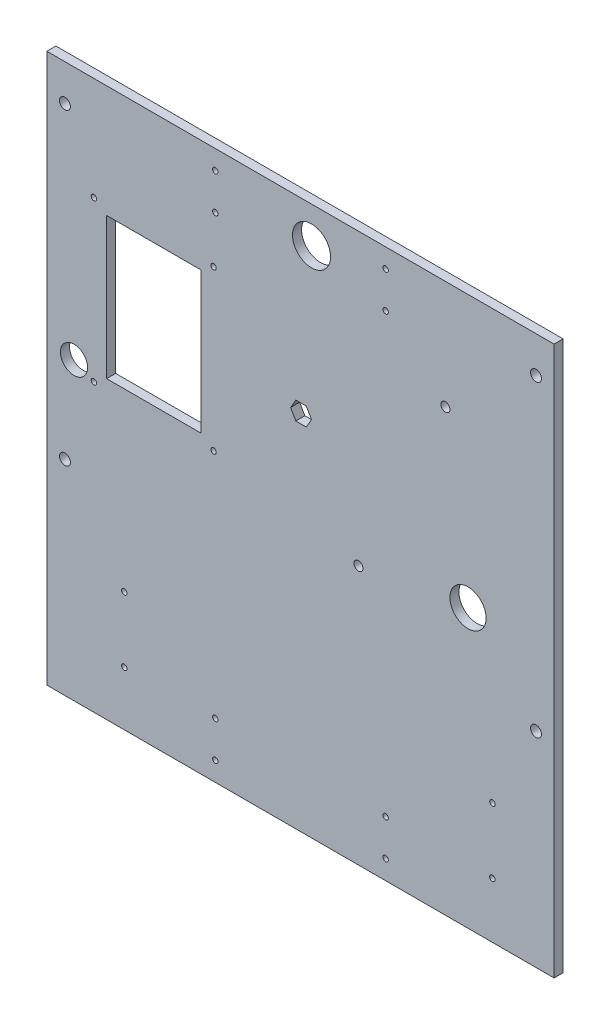
SolidWorks part; units mm, degrees
ref_plane "Plan de face" through (0, 0, 0) normal (0, 0, 1) x (1, 0, 0)
ref_plane "Plan de dessus" through (0, 0, 0) normal (0, 1, 0) x (1, 0, 0)
ref_plane "Plan de droite" through (0, 0, 0) normal (1, 0, 0) x (0, 0, -1)
sketch "Esquisse1" plane through (0, 0, 0) normal (0, 0, 1) x (1, 0, 0)
  line L1 (0, 0) -> (280, 0)
  line L2 (0, 0) -> (0, 210)
  line L3 (0, 210) -> (280, 210)
  line L4 (280, 0) -> (280, 210)
  dimension "D1" = 210
  dimension "D2" = 280
extrude "Boss.-Extru.1" add sketch "Esquisse1" along normal blind 5
sketch "Esquisse2" plane through (0, 0, 0) normal (0, 0, 1) x (1, 0, 0)
  line L1 (85, 148) -> (33, 148)
  line L2 (0, 0) -> (280, 0) construction
  line L3 (0, 0) -> (0, 210) construction
  line L4 (0, 210) -> (280, 210) construction
  line L5 (280, 0) -> (280, 210) construction
  line L6 (85, 148) -> (85, 70)
  line L7 (137.4335, 111.9714) -> (134.5467, 106.9714)
  line L8 (134.5467, 106.9714) -> (137.4335, 101.9714)
  line L9 (137.4335, 101.9714) -> (143.207, 101.9714)
  line L10 (143.207, 101.9714) -> (146.0937, 106.9714)
  line L11 (146.0937, 106.9714) -> (143.207, 111.9714)
  line L12 (143.207, 111.9714) -> (137.4335, 111.9714)
  line L13 (85, 70) -> (33, 70)
  line L14 (33, 148) -> (33, 70)
  circle A0 centre (270, 190) radius 3
  circle A1 centre (10, 190) radius 3
  circle A2 centre (10, 20) radius 3
  circle A3 centre (270, 20) radius 3
  circle A4 centre (140.3202, 106.9714) radius 5 construction
  circle A5 centre (220, 150) radius 2.5
  circle A6 centre (172, 50) radius 2.5
  circle A7 centre (92, 153) radius 1.5
  circle A8 centre (26, 153) radius 1.5
  circle A9 centre (92, 65) radius 1.5
  circle A10 centre (26, 65) radius 1.5
  circle A11 centre (15, 70) radius 7.5
  circle A12 centre (146.0937, 190) radius 10.5
  circle A13 centre (232.4771, 60.1974) radius 10
  dimension "D1" = 6
  dimension "D2" = 6
  dimension "D3" = 6
  dimension "D4" = 6
  dimension "D5" = 20
  dimension "D6" = 10
  dimension "D7" = 20
  dimension "D8" = 10
  dimension "D9" = 10
  dimension "D10" = 20
  dimension "D11" = 10
  dimension "D12" = 20
  dimension "D13" = 10
  dimension "D14" = 100
  dimension "D15" = 48
  dimension "D16" = 5
  dimension "D17" = 5
  dimension "D19" = 50
  dimension "D26" = 7
  dimension "D27" = 5
  dimension "D29" = 7
  dimension "D30" = 5
  dimension "D32" = 3
  dimension "D33" = 3
  dimension "D34" = 3
  dimension "D35" = 3
  dimension "D38" = 15
  dimension "D39" = 21
  dimension "D40" = 20
  dimension "D18" = 60
  dimension "D20" = 52
  dimension "D21" = 78
  dimension "D22" = 70
  dimension "D23" = 85
  dimension "D24" = 5
  dimension "D25" = 7
  dimension "D28" = 5
  dimension "D31" = 7
  dimension "D36" = 18
extrude "Enlèv. mat.-Extru.1" cut sketch "Esquisse2" along normal through all
sketch "Esquisse5" plane through (0, 0, 0) normal (0, 0, -1) x (-1, 0, 0)
  circle A0 centre (-93, 179.4) radius 1.5
  circle A1 centre (-93, 199.4) radius 1.5
  circle A2 centre (-187, 199.4) radius 1.5
  circle A3 centre (-187, 179.4) radius 1.5
  dimension "D1" = 3
  dimension "D2" = 3
  dimension "D3" = 3
  dimension "D4" = 3
extrude "Enlèv. mat.-Extru.3" cut sketch "Esquisse5" against normal through all
sketch "Esquisse6" plane through (0, 0, 0) normal (0, 0, -1) x (-1, 0, 0)
  line L1 (-280, 0) -> (0, 0)
  line L2 (-280, 0) -> (-280, -93)
  line L3 (-280, -93) -> (0, -93)
  line L4 (0, 0) -> (0, -93)
  point P5 (-280, -46.5)
  dimension "D1" = 93
  dimension "D2" = 280
extrude "Boss.-Extru.4" add sketch "Esquisse6" against normal blind 5
sketch "Esquisse7" plane through (0, 0, 0) normal (0, 0, -1) x (-1, 0, 0)
  circle A0 centre (-42.7853, -27.0556) radius 1.5
  circle A3 centre (-42.7733, -63.0396) radius 1.5
  dimension "D3" = 3
  dimension "D4" = 3
extrude "Enlèv. mat.-Extru.4" cut sketch "Esquisse7" against normal through all
sketch "Esquisse8" plane through (0, 0, 0) normal (0, 0, -1) x (-1, 0, 0)
  circle A0 centre (-245.9449, -62.3449) radius 1.5
  circle A1 centre (-245.9449, -26.3609) radius 1.5
  dimension "D2" = 3
  dimension "D3" = 3
extrude "Enlèv. mat.-Extru.5" cut sketch "Esquisse8" against normal through all
sketch "Esquisse9" plane through (0, 0, 0) normal (0, 0, -1) x (-1, 0, 0)
  circle A0 centre (-93, -62.4) radius 1.5
  circle A1 centre (-93, -82.4) radius 1.5
  circle A2 centre (-93, -82.4) radius 1.5 construction
  circle A3 centre (-187, -82.4) radius 1.5
  circle A4 centre (-187, -62.4) radius 1.5
  dimension "D1" = 3
  dimension "D2" = 3
  dimension "D3" = 0
  dimension "D4" = 3
  dimension "D5" = 3
extrude "Enlèv. mat.-Extru.6" cut sketch "Esquisse9" against normal through all
